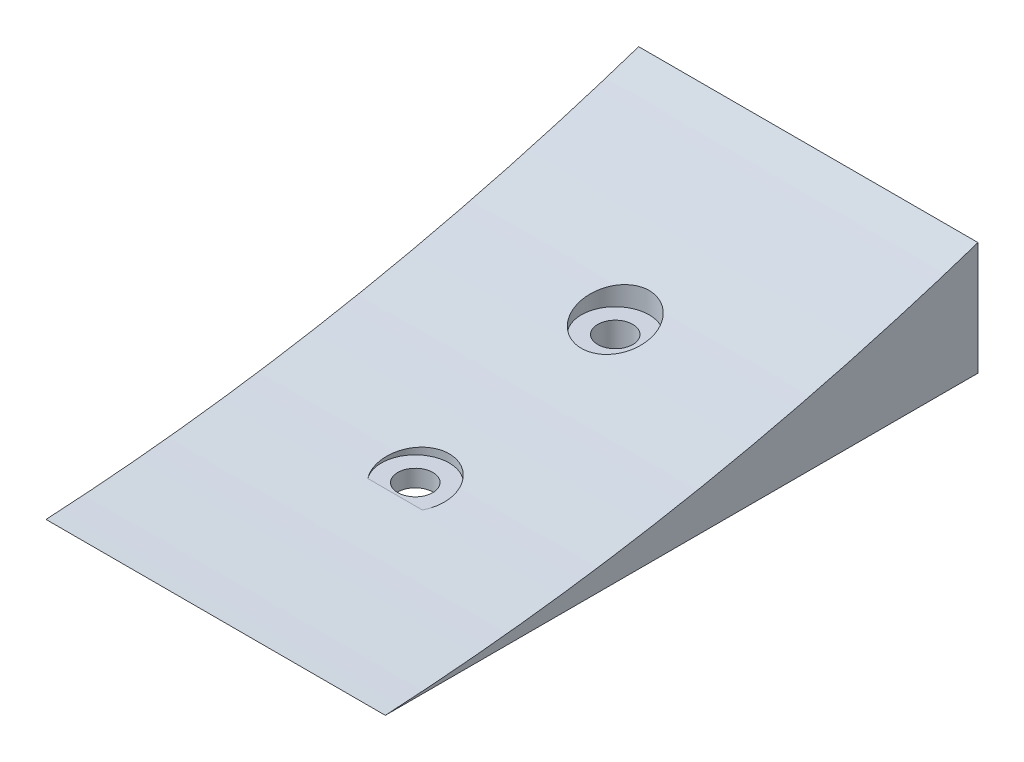
SolidWorks part; units mm, degrees
ref_plane "Front Plane" through (0, 0, 0) normal (0, 0, 1) x (1, 0, 0)
ref_plane "Top Plane" through (0, 0, 0) normal (0, 1, 0) x (1, 0, 0)
ref_plane "Right Plane" through (0, 0, 0) normal (1, 0, 0) x (0, 0, -1)
sketch "Sketch1" plane through (0, 0, 0) normal (0, 1, 0) x (1, 0, 0)
  line L1 (0, 0) -> (30, 0)
  line L2 (0, 0) -> (0, 52.4)
  line L3 (0, 52.4) -> (30, 52.4)
  line L4 (30, 0) -> (30, 52.4)
  dimension "D1" = 52.4
  dimension "D2" = 30
extrude "Boss-Extrude1" add sketch "Sketch1" along normal blind 10
sketch "Sketch2" plane through (30, 0, 0) normal (1, 0, 0) x (0, 0, -1)
  line L0 (52.4, 10) -> (0, 10)
  line L1 (0, 10) -> (0, 0)
  spline S0 degree 2 poles (52.4, 10) (26.7976, 1.4648) (0, 0) knots 0 0 0 1 1 1
extrude "Cut-Extrude1" cut sketch "Sketch2" against normal blind 30
sketch "Sketch3" plane through (0, 0, 0) normal (0, -1, 0) x (-1, 0, 0)
  line L0 (-30, 52.4) -> (0, 52.4) construction
  line L1 (-30, 52.4) -> (0, 52.4) construction
  line L2 (-15, 52.4) -> (-15, 0) construction
  line L3 (0, 0) -> (-30, 0) construction
  circle A0 centre (-15, 35.33) radius 1.55
  circle A1 centre (-15, 17.65) radius 1.55
  circle A2 centre (-15, 35.33) radius 3
  circle A3 centre (-15, 17.65) radius 3
  dimension "D2" = 3.1
  dimension "D3" = 3.1
  dimension "D5" = 6
  dimension "D6" = 6
  dimension "D1" = 17.07
  dimension "D4" = 17.68
extrude "Cut-Extrude2" cut sketch "Sketch3" against normal blind 14 contours A0 | A1
extrude "Cut-Extrude3" cut sketch "Sketch3<4>" against normal blind 12 from offset 4 contours A2 A0 region at (17.9151, 0, -35.33) offset against normal yes
sketch "Sketch3<4>" plane through (0, 0, 0) normal (0, -1, 0) x (-1, 0, 0) same geometry as "Sketch3"
extrude "Cut-Extrude4" cut sketch "Sketch3<7>" against normal through all from offset 1.5 contours A3 A1 region at (17.9151, 0, -17.65) offset against normal yes
sketch "Sketch3<7>" plane through (0, 0, 0) normal (0, -1, 0) x (-1, 0, 0) same geometry as "Sketch3"
